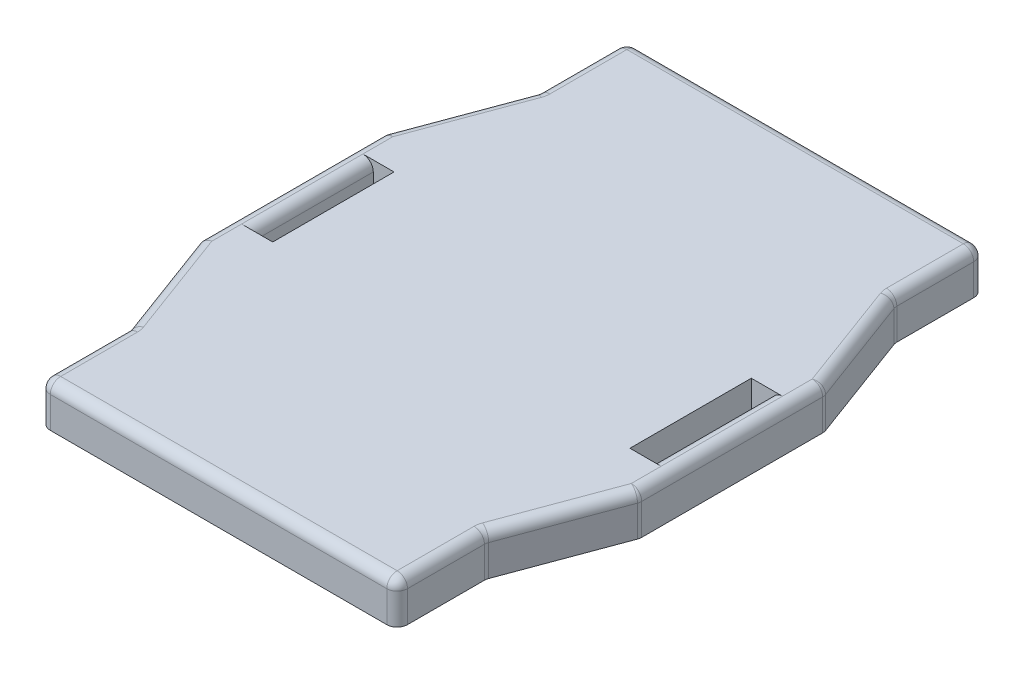
SolidWorks part; units mm, degrees
note: The reader was unsure of these and kept them because the rebuilt part matched: shared geometry of "Sketch1<3>".
material "ABS"
ref_plane "Front Plane" through (0, 0, 0) normal (0, 0, 1) x (1, 0, 0)
ref_plane "Top Plane" through (0, 0, 0) normal (0, 1, 0) x (1, 0, 0)
ref_plane "Right Plane" through (0, 0, 0) normal (1, 0, 0) x (0, 0, -1)
sketch "Sketch1" plane through (0, 0, 0) normal (0, 1, 0) x (1, 0, 0)
  line L0 (43, 70.65) -> (-43, 70.65)
  line L1 (37, 64.65) -> (-37, 64.65)
  line L2 (37, 64.65) -> (37, -64.65)
  line L3 (37, -64.65) -> (-37, -64.65)
  line L4 (-37, 64.65) -> (-37, -64.65)
  line L5 (37, 64.65) -> (-37, -64.65) construction
  line L6 (37, -64.65) -> (-37, 64.65) construction
  line L7 (-43, 70.65) -> (-43, -70.65)
  line L8 (43, -70.65) -> (-43, -70.65)
  line L9 (43, 70.65) -> (43, -70.65)
  point P0 (0, 0)
  dimension "D1" = 74
  dimension "D2" = 129.3
  dimension "D3" = 6
extrude "Boss-Extrude1" add sketch "Sketch1" along normal blind 4 contours L7 L8 L9 L0
extrude "Boss-Extrude2" add sketch "Sketch1<3>" against normal blind 6
sketch "Sketch1<3>" plane through (0, 0, 0) normal (0, 1, 0) x (1, 0, 0) same geometry as "Sketch1"
sketch "Sketch2" plane through (0, 4, 0) normal (0, 1, 0) x (1, 0, 0)
  line L0 (0, 0) -> (-72.118, 0) construction
  line L1 (0, 0) -> (0, -41.3244) construction
  line L2 (-43, 70.65) -> (-43, -70.65) construction
  line L3 (-53, 22.225) -> (-43, 22.225) construction
  line L4 (-53, 22.225) -> (-53, -22.225)
  line L5 (-53, -22.225) -> (-43, -22.225) construction
  line L6 (-43, 22.225) -> (-43, 0)
  line L7 (-53, 22.225) -> (-43, -22.225) construction
  line L8 (-53, -22.225) -> (-43, 22.225) construction
  line L9 (43, 22.225) -> (43, 14.605)
  line L10 (-48, -14.605) -> (-43, -14.605)
  line L11 (-48, -14.605) -> (-48, 14.605)
  line L12 (-48, 14.605) -> (-43, 14.605)
  line L13 (-43, 0) -> (-43, 14.605)
  line L14 (-48, -14.605) -> (-43, 14.605) construction
  line L15 (-48, 14.605) -> (-43, -14.605) construction
  line L16 (53, 22.225) -> (43, 22.225)
  line L17 (48, 14.605) -> (43, 14.605)
  line L18 (48, -14.605) -> (43, -14.605)
  line L19 (53, -22.225) -> (43, -22.225) construction
  line L20 (48, -14.605) -> (48, 14.605)
  line L21 (53, 22.225) -> (53, -22.225)
  line L22 (-43, -14.605) -> (-43, -22.225)
  line L23 (43, -14.605) -> (43, -22.225)
  line L24 (-53, -22.225) -> (-43, -49.1886)
  line L25 (-43, -49.1886) -> (-43, -22.225)
  line L26 (-53, 22.225) -> (-43, 49.1886)
  line L27 (-43, 49.1886) -> (-43, 22.225)
  line L28 (53, 22.225) -> (43, 49.1886)
  line L29 (43, 70.65) -> (43, -70.65) construction
  line L30 (53, -22.225) -> (43, -49.1886)
  line L31 (43, 49.1886) -> (43, 22.225)
  line L32 (43, -49.1886) -> (43, -22.225)
  line L33 (-43, -49.1886) -> (-43, -22.225)
  point P3 (-48, 0)
  point P11 (-45.5, 0)
  line M4 (-43, 70.65) -> (-43, -70.65)
  dimension "D1" = 29.21
  dimension "D2" = 44.45
  dimension "D3" = 10
  dimension "D4" = 5
extrude "Boss-Extrude3" add sketch "Sketch2" against normal up to vertex (10 mm away) contours L11 L12 L3 L4 L5 L10 M4 | L21 L30 L32 L23 L18 L20 L17 L9 L31 L28
fillet "Fillet2" radius 2.5 25 edges at (0, 4, 70.65) (43, 4, -59.9193) (-43, 4, 59.9193) (0, 4, -70.65) (-48, 4, -35.7068) (-53, -1, -22.225) (-43, -1, -49.1886) (-43, -1, 49.1886) (-53, 4, 0) (-48, 4, 35.7068) (-48, 4, 0) (43, 4, 59.9193) (43, -1, -49.1886) (53, 4, 0) (53, -1, -22.225) (48, 4, 35.7068) (53, -1, 22.225) (43, -1, 49.1886) (48, 4, 0) (-43, 4, -59.9193) (48, 4, -35.7068) (43, -1, -70.65) (43, -1, 70.65) (-43, -1, 70.65) (-43, -1, -70.65)
